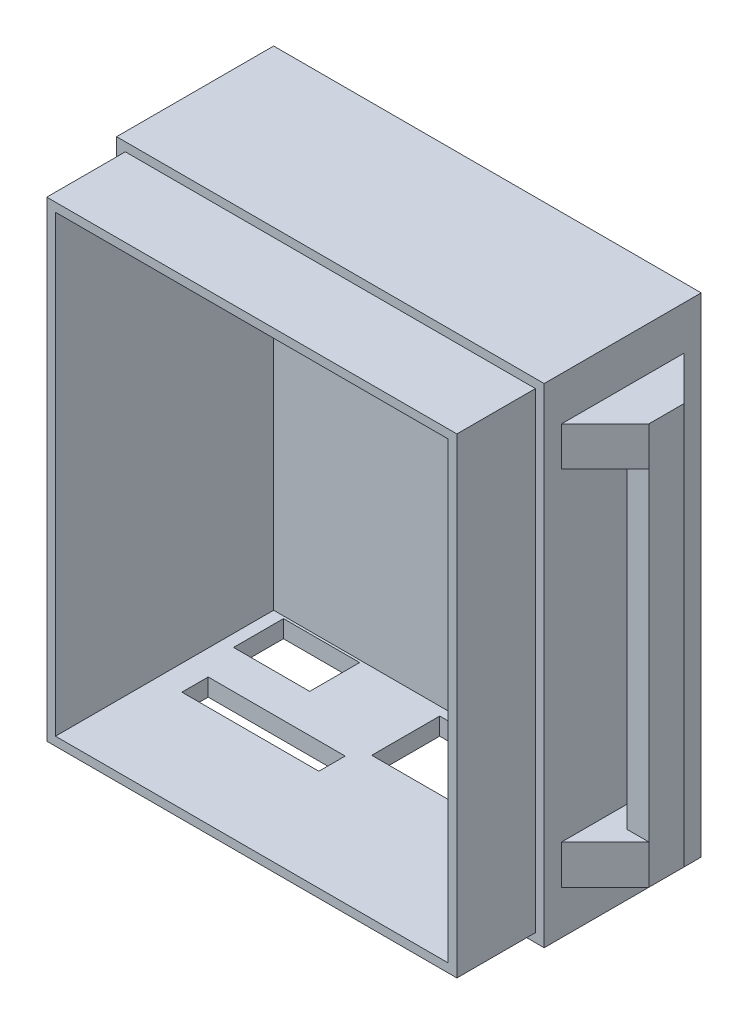
SolidWorks part; units mm, degrees
ref_plane "Piano frontale" through (0, 0, 0) normal (0, 0, 1) x (1, 0, 0)
ref_plane "Piano superiore" through (0, 0, 0) normal (0, 1, 0) x (1, 0, 0)
ref_plane "Piano destro" through (0, 0, 0) normal (1, 0, 0) x (0, 0, -1)
sketch "Schizzo1" plane through (0, 0, 0) normal (0, 0, 1) x (1, 0, 0)
  line L1 (0, 0) -> (49, 0)
  line L2 (0, 0) -> (0, 56)
  line L3 (0, 56) -> (49, 56)
  line L4 (49, 0) -> (49, 56)
  dimension "D1" = 49
  dimension "D2" = 56
extrude "Estrusione-Estrusione1" add sketch "Schizzo1" along normal blind 2
sketch "Schizzo3" plane through (0, 0, 2) normal (0, 0, 1) x (1, 0, 0)
  line L0 (49, 0) -> (49, 56) construction
  line L1 (0, 56) -> (49, 56)
  line L2 (0, 56) -> (0, 54)
  line L3 (0, 54) -> (49, 54)
  line L4 (49, 56) -> (49, 54)
  dimension "D1" = 2
extrude "Estrusione-Estrusione2" add sketch "Schizzo3" along normal blind 25
sketch "Schizzo4" plane through (0, 0, 2) normal (0, 0, 1) x (1, 0, 0)
  line L0 (0, 0) -> (49, 0) construction
  line L1 (49, 54) -> (47, 54)
  line L2 (49, 54) -> (49, 0)
  line L3 (49, 0) -> (47, 0)
  line L4 (47, 54) -> (47, 0)
  dimension "D1" = 2
extrude "Estrusione-Estrusione3" add sketch "Schizzo4" along normal blind 25
sketch "Schizzo5" plane through (0, 0, 2) normal (0, 0, 1) x (1, 0, 0)
  line L0 (0, 54) -> (0, 0) construction
  line L1 (47, 0) -> (0, 0)
  line L2 (47, 0) -> (47, 2)
  line L3 (47, 2) -> (0, 2)
  line L4 (0, 0) -> (0, 2)
  dimension "D1" = 2
extrude "Estrusione-Estrusione4" add sketch "Schizzo5" along normal blind 25
sketch "Schizzo6" plane through (0, 0, 2) normal (0, 0, 1) x (1, 0, 0)
  line L0 (47, 2) -> (0, 2) construction
  line L1 (0, 54) -> (2, 54)
  line L2 (0, 54) -> (0, 2)
  line L3 (0, 2) -> (2, 2)
  line L4 (2, 54) -> (2, 2)
  dimension "D1" = 2
extrude "Estrusione-Estrusione5" add sketch "Schizzo6" along normal blind 25
sketch "Schizzo7" plane through (0, 0, 2) normal (0, 0, 1) x (1, 0, 0)
  line L1 (2, 2) -> (2, 54) construction
  line L4 (2, 43.7) -> (27, 43.7)
  line L5 (2, 43.7) -> (2, 46.7)
  line L6 (2, 46.7) -> (27, 46.7)
  line L7 (27, 43.7) -> (27, 46.7)
  dimension "D2" = 3
  dimension "D3" = 25
extrude "Estrusione-Estrusione6" add sketch "Schizzo7" along normal blind 13.3
sketch "Schizzo9" plane through (0, 0, 2) normal (0, 0, 1) x (1, 0, 0)
  line L0 (2, 54) -> (47, 54) construction
  line L1 (47, 2) -> (43.5, 2)
  line L2 (47, 2) -> (47, 54)
  line L3 (47, 54) -> (43.5, 54)
  line L4 (43.5, 2) -> (43.5, 54)
  dimension "D1" = 3.5
extrude "Estrusione-Estrusione7" add sketch "Schizzo9" along normal blind 13.3
sketch "Schizzo10" plane through (0, 0, 15.3) normal (0, 0, 1) x (1, 0, 0)
  line L5 (4, 45.95) -> (8, 45.95)
  line L6 (4, 45.95) -> (4, 44.45)
  line L7 (4, 44.45) -> (8, 44.45)
  line L8 (8, 45.95) -> (8, 44.45)
  line L11 (26, 45.95) -> (22, 45.95)
  line L12 (26, 45.95) -> (26, 44.45)
  line L13 (26, 44.45) -> (22, 44.45)
  line L14 (22, 45.95) -> (22, 44.45)
  point P17 (26, 45.2)
  dimension "D3" = 1.5
  dimension "D4" = 4
  dimension "D6" = 4
extrude "Taglio-Estrusione1" cut sketch "Schizzo10" against normal blind 6
sketch "Schizzo11" plane through (0, 0, 15.3) normal (0, 0, 1) x (1, 0, 0)
  line L4 (46, 45.95) -> (44.5, 45.95)
  line L5 (46, 45.95) -> (46, 44.45)
  line L6 (46, 44.45) -> (44.5, 44.45)
  line L7 (44.5, 45.95) -> (44.5, 44.45)
  dimension "D2" = 1.5
  dimension "D3" = 1.5
extrude "Taglio-Estrusione2" cut sketch "Schizzo11" against normal blind 6
sketch "Schizzo12" plane through (0, 45.95, 0) normal (0, -1, 0) x (-1, 0, 0)
  line L0 (-8, -9.3) -> (-8, -15.3) construction
  line L1 (-4, -15.3) -> (-8, -15.3)
  line L2 (-4, -15.3) -> (-4, -14.3)
  line L3 (-4, -14.3) -> (-8, -14.3)
  line L4 (-8, -15.3) -> (-8, -14.3)
  dimension "D1" = 1
extrude "Taglio-Estrusione3" cut sketch "Schizzo12" against normal blind 0.75
sketch "Schizzo13" plane through (0, 44.45, 0) normal (0, 1, 0) x (1, 0, 0)
  line L0 (8, -9.3) -> (8, -15.3) construction
  line L1 (4, -15.3) -> (8, -15.3)
  line L2 (4, -15.3) -> (4, -14.3)
  line L3 (4, -14.3) -> (8, -14.3)
  line L4 (8, -15.3) -> (8, -14.3)
  dimension "D1" = 1
extrude "Taglio-Estrusione4" cut sketch "Schizzo13" against normal blind 0.75
sketch "Schizzo14" plane through (0, 45.95, 0) normal (0, -1, 0) x (-1, 0, 0)
  line L0 (-26, -9.3) -> (-26, -15.3) construction
  line L1 (-22, -15.3) -> (-26, -15.3)
  line L2 (-22, -15.3) -> (-22, -14.3)
  line L3 (-22, -14.3) -> (-26, -14.3)
  line L4 (-26, -15.3) -> (-26, -14.3)
  dimension "D1" = 1
extrude "Taglio-Estrusione5" cut sketch "Schizzo14" against normal blind 0.75
sketch "Schizzo15" plane through (0, 44.45, 0) normal (0, 1, 0) x (1, 0, 0)
  line L0 (26, -9.3) -> (26, -15.3) construction
  line L1 (22, -15.3) -> (26, -15.3)
  line L2 (22, -15.3) -> (22, -14.3)
  line L3 (22, -14.3) -> (26, -14.3)
  line L4 (26, -15.3) -> (26, -14.3)
  dimension "D1" = 1
extrude "Taglio-Estrusione6" cut sketch "Schizzo15" against normal blind 0.75
sketch "Schizzo21" plane through (0, 0, 15.3) normal (0, 0, 1) x (1, 0, 0)
  line L0 (43.5, 54) -> (43.5, 2) construction
  line L1 (44.5, 45.95) -> (43.5, 45.95)
  line L2 (44.5, 45.95) -> (44.5, 44.45)
  line L3 (44.5, 44.45) -> (43.5, 44.45)
  line L4 (43.5, 45.95) -> (43.5, 44.45)
extrude "Taglio-Estrusione7" cut sketch "Schizzo21" against normal blind 1
sketch "Schizzo23" plane through (0, 0, 15.3) normal (0, 0, 1) x (1, 0, 0)
  line L1 (43.5, 45.95) -> (46, 45.95)
  line L2 (43.5, 45.95) -> (43.5, 46.7)
  line L3 (43.5, 46.7) -> (46, 46.7)
  line L4 (46, 45.95) -> (46, 46.7)
  dimension "D1" = 0.75
extrude "Taglio-Estrusione8" cut sketch "Schizzo23" against normal blind 1
sketch "Schizzo24" plane through (0, 0, 15.3) normal (0, 0, 1) x (1, 0, 0)
  line L1 (43.5, 44.45) -> (45.9968, 44.45)
  line L2 (43.5, 44.45) -> (43.5, 43.7)
  line L3 (43.5, 43.7) -> (45.9968, 43.7)
  line L4 (45.9968, 44.45) -> (45.9968, 43.7)
  dimension "D1" = 0.75
extrude "Taglio-Estrusione9" cut sketch "Schizzo24" against normal blind 1
sketch "Schizzo26" plane through (0, 0, 15.3) normal (0, 0, 1) x (1, 0, 0)
  line L0 (47, 54) -> (47, 2) construction
  line L1 (45.9968, 43.7) -> (47, 43.7)
  line L2 (45.9968, 43.7) -> (45.9968, 46.7)
  line L3 (45.9968, 46.7) -> (47, 46.7)
  line L4 (47, 43.7) -> (47, 46.7)
  dimension "D1" = 3
extrude "Taglio-Estrusione10" cut sketch "Schizzo26" against normal blind 1
sketch "Schizzo27" plane through (0, 0, 15.3) normal (0, 0, 1) x (1, 0, 0)
  line L1 (26, 46.7) -> (27, 46.7)
  line L2 (26, 46.7) -> (26, 43.7)
  line L3 (26, 43.7) -> (27, 43.7)
  line L4 (27, 46.7) -> (27, 43.7)
extrude "Taglio-Estrusione11" cut sketch "Schizzo27" against normal blind 1
sketch "Schizzo28" plane through (0, 0, 15.3) normal (0, 0, 1) x (1, 0, 0)
  line L1 (47, 2) -> (47, 43.7) construction
  line L2 (43.5, 43.7) -> (43.5, 2) construction
  line L3 (47, 13.3) -> (43.5, 13.3)
  line L4 (47, 13.3) -> (47, 17.3)
  line L5 (47, 17.3) -> (43.5, 17.3)
  line L6 (43.5, 13.3) -> (43.5, 17.3)
  line L7 (47, 17.3) -> (26, 17.3) construction
extrude "Taglio-Estrusione12" cut sketch "Schizzo28" against normal blind 1
sketch "Schizzo33" plane through (0, 0, 15.3) normal (0, 0, 1) x (1, 0, 0)
  line L1 (43.5, 43.7) -> (43.5, 17.3) construction
  line L3 (43.5, 28.5) -> (47, 28.5)
  line L4 (43.5, 28.5) -> (43.5, 32.5)
  line L5 (43.5, 32.5) -> (47, 32.5)
  line L6 (47, 28.5) -> (47, 32.5)
extrude "Taglio-Estrusione16" cut sketch "Schizzo33" against normal blind 1
sketch "Schizzo34" plane through (0, 0, 0) normal (0, -1, 0) x (1, 0, 0)
  line L1 (3.3938, 7.9878) -> (12.1185, 7.9878)
  line L2 (3.3938, 7.9878) -> (3.3938, 2.267)
  line L3 (3.3938, 2.267) -> (12.1185, 2.267)
  line L4 (12.1185, 7.9878) -> (12.1185, 2.267)
extrude "Taglio-Estrusione17" cut sketch "Schizzo34" against normal blind 2
sketch "Schizzo36" plane through (0, 0, 0) normal (0, -1, 0) x (1, 0, 0)
  line L1 (22.0157, 10.7757) -> (40.2471, 10.7757)
  line L2 (22.0157, 10.7757) -> (22.0157, 2.9855)
  line L3 (22.0157, 2.9855) -> (40.2471, 2.9855)
  line L4 (40.2471, 10.7757) -> (40.2471, 2.9855)
extrude "Taglio-Estrusione18" cut sketch "Schizzo36" against normal blind 2
sketch "Schizzo37" plane through (0, 0, 0) normal (0, -1, 0) x (-1, 0, 0)
  line L1 (-4.8742, -15.3897) -> (-20.5692, -15.3897)
  line L2 (-4.8742, -15.3897) -> (-4.8742, -12.3745)
  line L3 (-4.8742, -12.3745) -> (-20.5692, -12.3745)
  line L4 (-20.5692, -15.3897) -> (-20.5692, -12.3745)
extrude "Taglio-Estrusione19" cut sketch "Schizzo37" against normal blind 2
sketch "Schizzo38" plane through (0, 0, 27) normal (0, 0, 1) x (1, 0, 0)
  line L0 (0, 0) -> (49, 0) construction
  line L1 (49, 56) -> (48, 56)
  line L2 (49, 56) -> (49, 0)
  line L3 (49, 0) -> (48, 0)
  line L4 (48, 56) -> (48, 0)
  dimension "D1" = 1
extrude "Taglio-Estrusione20" cut sketch "Schizzo38" against normal blind 9
sketch "Schizzo39" plane through (0, 0, 27) normal (0, 0, 1) x (1, 0, 0)
  line L0 (0, 56) -> (0, 0) construction
  line L1 (48, 0) -> (0, 0)
  line L2 (48, 0) -> (48, 1)
  line L3 (48, 1) -> (0, 1)
  line L4 (0, 0) -> (0, 1)
  dimension "D1" = 1
extrude "Taglio-Estrusione21" cut sketch "Schizzo39" against normal blind 9
sketch "Schizzo40" plane through (0, 0, 27) normal (0, 0, 1) x (1, 0, 0)
  line L0 (48, 56) -> (0, 56) construction
  line L1 (0, 1) -> (1, 1)
  line L2 (0, 1) -> (0, 56)
  line L3 (0, 56) -> (1, 56)
  line L4 (1, 1) -> (1, 56)
  dimension "D1" = 1
extrude "Taglio-Estrusione22" cut sketch "Schizzo40" against normal blind 9
sketch "Schizzo41" plane through (0, 0, 27) normal (0, 0, 1) x (1, 0, 0)
  line L0 (48, 56) -> (48, 1) construction
  line L1 (1, 56) -> (48, 56)
  line L2 (1, 56) -> (1, 55)
  line L3 (1, 55) -> (48, 55)
  line L4 (48, 56) -> (48, 55)
  dimension "D1" = 1
extrude "Taglio-Estrusione23" cut sketch "Schizzo41" against normal blind 9
sketch "Schizzo42" plane through (49, 0, 0) normal (1, 0, 0) x (0, 0, -1)
  line L4 (-16, 5) -> (-2, 5)
  line L5 (-16, 5) -> (-16, 9.5)
  line L6 (-16, 9.5) -> (-2, 9.5)
  line L7 (-2, 5) -> (-2, 9.5)
  dimension "D3" = 4.5
  dimension "D4" = 14
extrude "Estrusione-Estrusione10" add sketch "Schizzo42" along normal blind 5
sketch "Schizzo44" plane through (0, 5, 0) normal (0, -1, 0) x (-1, 0, 0)
  line L0 (-54, -16) -> (-54, -11)
  line L1 (-54, -16) -> (-54, -2) construction
  line L2 (-54, -11) -> (-49, -16)
  line L3 (-49, -16) -> (-49, -2) construction
  line L4 (-49, -16) -> (-54, -16)
  dimension "D1" = 5
extrude "Taglio-Estrusione24" cut sketch "Schizzo44" against normal blind 6
sketch "Schizzo45" plane through (0, 5, 0) normal (0, -1, 0) x (-1, 0, 0)
  line L0 (-54, -2) -> (-54, -7)
  line L1 (-54, -11) -> (-54, -2) construction
  line L2 (-54, -7) -> (-49, -2)
  line L3 (-49, -2) -> (-54, -2)
  dimension "D1" = 5
extrude "Taglio-Estrusione25" cut sketch "Schizzo45" against normal blind 6
sketch "Schizzo48" plane through (0, 9.5, 0) normal (0, 1, 0) x (1, 0, 0)
  line L1 (54, -7) -> (51.5, -7)
  line L2 (54, -7) -> (54, -11)
  line L3 (54, -11) -> (51.5, -11)
  line L4 (51.5, -7) -> (51.5, -11)
  dimension "D1" = 4
  dimension "D2" = 2.5
extrude "Estrusione-Estrusione11" add sketch "Schizzo48" along normal blind 41.5
sketch "Schizzo49" plane through (51.5, 0, 0) normal (-1, 0, 0) x (0, 0, 1)
  line L0 (11, 51) -> (11, 9.5) construction
  line L1 (7, 51) -> (11, 51)
  line L2 (7, 51) -> (7, 46.5)
  line L3 (7, 46.5) -> (11, 46.5)
  line L4 (11, 51) -> (11, 46.5)
  dimension "D1" = 4.5
extrude "Estrusione-Estrusione12" add sketch "Schizzo49" along normal blind 2.5
sketch "Schizzo51" plane through (49, 0, 0) normal (1, 0, 0) x (0, 0, -1)
  line L1 (-7, 51) -> (-2, 51)
  line L2 (-7, 51) -> (-7, 46.5)
  line L3 (-7, 46.5) -> (-2, 46.5)
  line L4 (-2, 51) -> (-2, 46.5)
  dimension "D1" = 4.5
  dimension "D2" = 5
extrude "Estrusione-Estrusione13" add sketch "Schizzo51" along normal blind 5
sketch "Schizzo52" plane through (0, 46.5, 0) normal (0, -1, 0) x (-1, 0, 0)
  line L0 (-49, -2) -> (-54, -7)
  line L1 (-54, -7) -> (-51.5, -7) construction
  line L2 (-54, -7) -> (-54, -2)
  line L3 (-54, -2) -> (-49, -2)
extrude "Taglio-Estrusione26" cut sketch "Schizzo52" against normal blind 5
sketch "Schizzo53" plane through (49, 0, 0) normal (1, 0, 0) x (0, 0, -1)
  line L1 (-11, 51) -> (-16, 51)
  line L2 (-11, 51) -> (-11, 46.5)
  line L3 (-11, 46.5) -> (-16, 46.5)
  line L4 (-16, 51) -> (-16, 46.5)
  dimension "D1" = 5
  dimension "D2" = 4.5
extrude "Estrusione-Estrusione14" add sketch "Schizzo53" along normal blind 5
sketch "Schizzo54" plane through (0, 46.5, 0) normal (0, -1, 0) x (-1, 0, 0)
  line L0 (-49, -16) -> (-54, -11)
  line L1 (-54, -11) -> (-54, -16)
  line L2 (-54, -16) -> (-49, -16)
extrude "Taglio-Estrusione27" cut sketch "Schizzo54" against normal blind 5
sketch "Schizzo55" plane through (0, 0, 0) normal (-1, 0, 0) x (0, 0, 1)
  line L4 (16, 5) -> (2, 5)
  line L5 (16, 5) -> (16, 9.5)
  line L6 (16, 9.5) -> (2, 9.5)
  line L7 (2, 5) -> (2, 9.5)
  dimension "D3" = 4.5
  dimension "D4" = 14
extrude "Estrusione-Estrusione15" add sketch "Schizzo55" along normal blind 5
